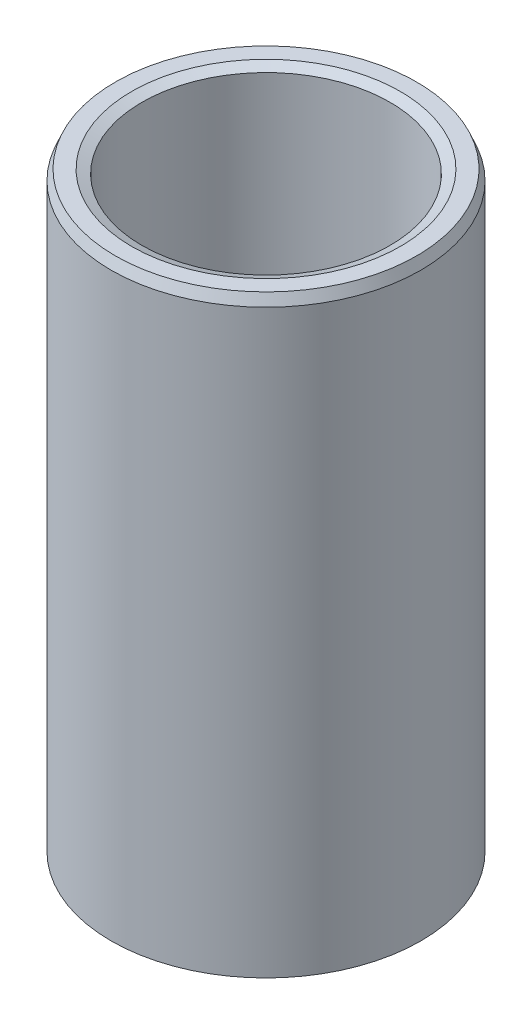
SolidWorks part; units mm, degrees
ref_plane "Front Plane" through (0, 0, 0) normal (0, 0, 1) x (1, 0, 0)
ref_plane "Top Plane" through (0, 0, 0) normal (0, 1, 0) x (1, 0, 0)
ref_plane "Right Plane" through (0, 0, 0) normal (1, 0, 0) x (0, 0, -1)
sketch "Sketch1" plane through (0, 0, 0) normal (0, 1, 0) x (1, 0, 0)
  circle A0 centre (0, 0) radius 52.5
  dimension "SLEEVE_OD" = 105
extrude "Boss-Extrude1" add sketch "Sketch1" along normal blind 201.8042
sketch "Sketch2" plane through (0, 0, 0) normal (0, 1, 0) x (1, 0, 0)
  circle A0 centre (0, 0) radius 42.0495
  dimension "BORE_D" = 84.0989
extrude "Cut-Extrude1" cut sketch "Sketch2" along normal through all
chamfer "Chamfer1" distance 3.4766 angle 22.502 4 edges at (0, 201.8042, 42.0495) (0, 0, 42.0495) (0, 0, 52.5) (0, 201.8042, 52.5) first distance on face at (0, 201.8042, 42.0495) first distance on face at (0, 0, 42.0495) first distance on face at (0, 201.8042, 52.5)
